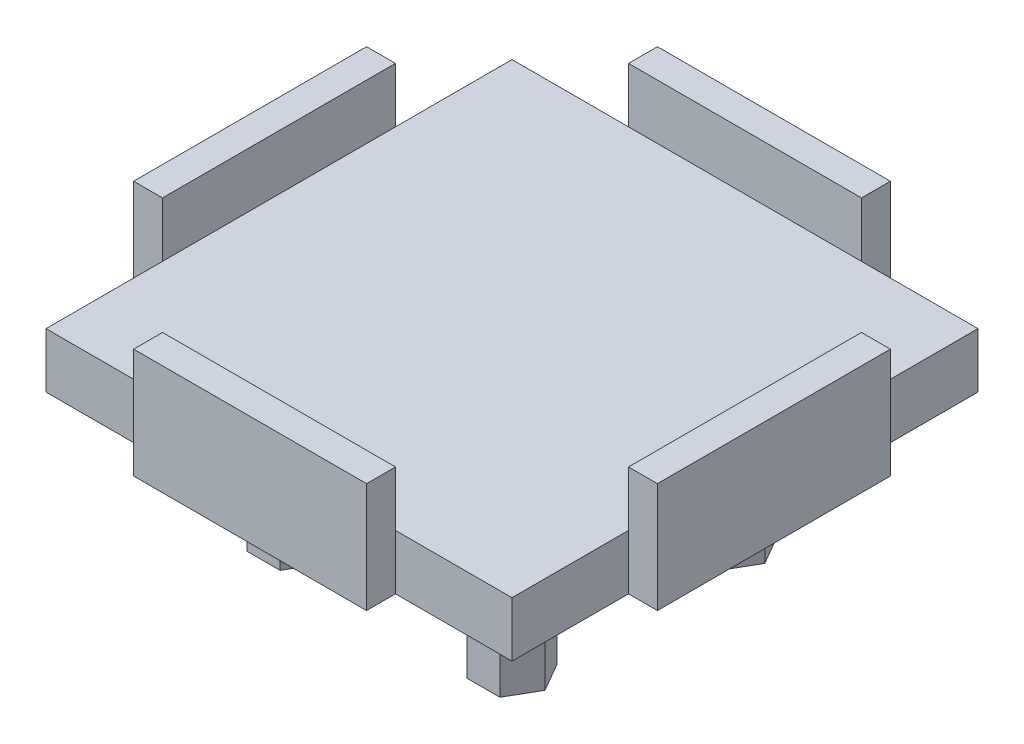
SolidWorks part; units mm, degrees
ref_plane "Front Plane" through (0, 0, 0) normal (0, 0, 1) x (1, 0, 0)
ref_plane "Top Plane" through (0, 0, 0) normal (0, 1, 0) x (1, 0, 0)
ref_plane "Right Plane" through (0, 0, 0) normal (1, 0, 0) x (0, 0, -1)
sketch "Sketch1" plane through (0, 0, 0) normal (0, 1, 0) x (1, 0, 0)
  line L1 (0, 0) -> (42.4, 0)
  line L2 (0, 0) -> (0, 42.4)
  line L3 (0, 42.4) -> (42.4, 42.4)
  line L4 (42.4, 0) -> (42.4, 42.4)
  dimension "D1" = 42.4
  dimension "D2" = 42.4
extrude "Boss-Extrude1" add sketch "Sketch1" along normal blind 5
sketch "Sketch3" plane through (0, 5, 0) normal (0, 1, 0) x (1, 0, 0)
  line L0 (0, 21.2) -> (42.4, 21.2) construction
  line L1 (0, 42.4) -> (0, 0) construction
  line L2 (42.4, 0) -> (42.4, 42.4) construction
  line L3 (21.2, 42.4) -> (21.2, 0) construction
  line L4 (42.4, 42.4) -> (0, 42.4) construction
  line L5 (0, 0) -> (42.4, 0) construction
  line L6 (0, 42.4) -> (42.4, 42.4) construction
  line L7 (10.6, 42.4) -> (31.8, 42.4) construction
  line L8 (45.0308, 31.8) -> (45.0308, 10.6)
  line L9 (10.6, 42.4) -> (31.8, 42.4)
  line L10 (10.6, 42.4) -> (10.6, 45.0308)
  line L11 (10.6, 45.0308) -> (31.8, 45.0308)
  line L12 (31.8, 42.4) -> (31.8, 45.0308)
  line L13 (42.4, 31.8) -> (45.0308, 31.8)
  line L14 (42.4, 31.8) -> (42.4, 10.6)
  line L15 (42.4, 10.6) -> (45.0308, 10.6)
  line L16 (31.8, -2.6308) -> (10.6, -2.6308)
  line L17 (31.8, 0) -> (31.8, -2.6308)
  line L18 (31.8, 0) -> (10.6, 0)
  line L19 (10.6, 0) -> (10.6, -2.6308)
  line L20 (-2.6308, 10.6) -> (-2.6308, 31.8)
  line L21 (0, 10.6) -> (-2.6308, 10.6)
  line L22 (0, 10.6) -> (0, 31.8)
  line L23 (0, 31.8) -> (-2.6308, 31.8)
  point P18 (21.2, 42.4)
  point P35 (21.2, 21.2)
  dimension "D1" = 2.6308
  dimension "D2" = 10.6
  dimension "D3" = 10.6
  dimension "D5" = 42.4
  dimension "D6" = 21.2
  dimension "D4" = 4
extrude "Boss-Extrude2" add sketch "Sketch3" along normal blind 5 and the other way blind 5
sketch "Sketch4" plane through (0, 0, 0) normal (0, -1, 0) x (1, 0, 0)
  line L0 (-2.6308, -21.2) -> (45.0308, -21.2) construction
  line L1 (-2.6308, -31.8) -> (-2.6308, -10.6) construction
  line L2 (45.0308, -10.6) -> (45.0308, -31.8) construction
  line L3 (21.2, 2.6308) -> (21.2, -45.0308) construction
  line L4 (10.6, 2.6308) -> (31.8, 2.6308) construction
  line L5 (31.8, -45.0308) -> (10.6, -45.0308) construction
  line L6 (21.2, -21.2) -> (31.2, -11.2) construction
  line L11 (31.2, -11.2) -> (11.2, -11.2) construction
  line L12 (11.2, -11.2) -> (11.2, -31.2) construction
  line L13 (11.2, -31.2) -> (31.2, -31.2) construction
  line L14 (31.2, -31.2) -> (31.2, -11.2) construction
  line L15 (32.7, -8.6019) -> (29.7, -8.6019)
  line L16 (9.7, -8.6019) -> (8.2, -11.2)
  line L17 (8.2, -11.2) -> (9.7, -13.7981)
  line L18 (9.7, -13.7981) -> (12.7, -13.7981)
  line L19 (12.7, -13.7981) -> (14.2, -11.2)
  line L20 (14.2, -11.2) -> (12.7, -8.6019)
  line L21 (12.7, -8.6019) -> (9.7, -8.6019)
  line L22 (29.7, -8.6019) -> (28.2, -11.2)
  line L23 (28.2, -11.2) -> (29.7, -13.7981)
  line L24 (29.7, -13.7981) -> (32.7, -13.7981)
  line L25 (32.7, -13.7981) -> (34.2, -11.2)
  line L26 (34.2, -11.2) -> (32.7, -8.6019)
  line L27 (32.7, -28.6019) -> (29.7, -28.6019)
  line L28 (29.7, -28.6019) -> (28.2, -31.2)
  line L29 (28.2, -31.2) -> (29.7, -33.7981)
  line L30 (29.7, -33.7981) -> (32.7, -33.7981)
  line L31 (32.7, -33.7981) -> (34.2, -31.2)
  line L32 (34.2, -31.2) -> (32.7, -28.6019)
  line L33 (12.7, -28.6019) -> (9.7, -28.6019)
  line L34 (9.7, -28.6019) -> (8.2, -31.2)
  line L35 (8.2, -31.2) -> (9.7, -33.7981)
  line L36 (9.7, -33.7981) -> (12.7, -33.7981)
  line L37 (12.7, -33.7981) -> (14.2, -31.2)
  line L38 (14.2, -31.2) -> (12.7, -28.6019)
  line L39 (29.7, -13.7981) -> (32.7, -8.6019) construction
  line L40 (9.7, -33.7981) -> (12.7, -28.6019) construction
  line L41 (29.7, -33.7981) -> (32.7, -28.6019) construction
  circle A0 centre (21.2, -21.2) radius 23.7023 construction
  circle A1 centre (11.2, -11.2) radius 3 construction
  circle A2 centre (21.2, -21.2) radius 14.1421 construction
  dimension "D1" = 20
  dimension "D2" = 6
  dimension "D4" = 2
  dimension "D5" = 2
extrude "Boss-Extrude3" add sketch "Sketch4" along normal blind 12
